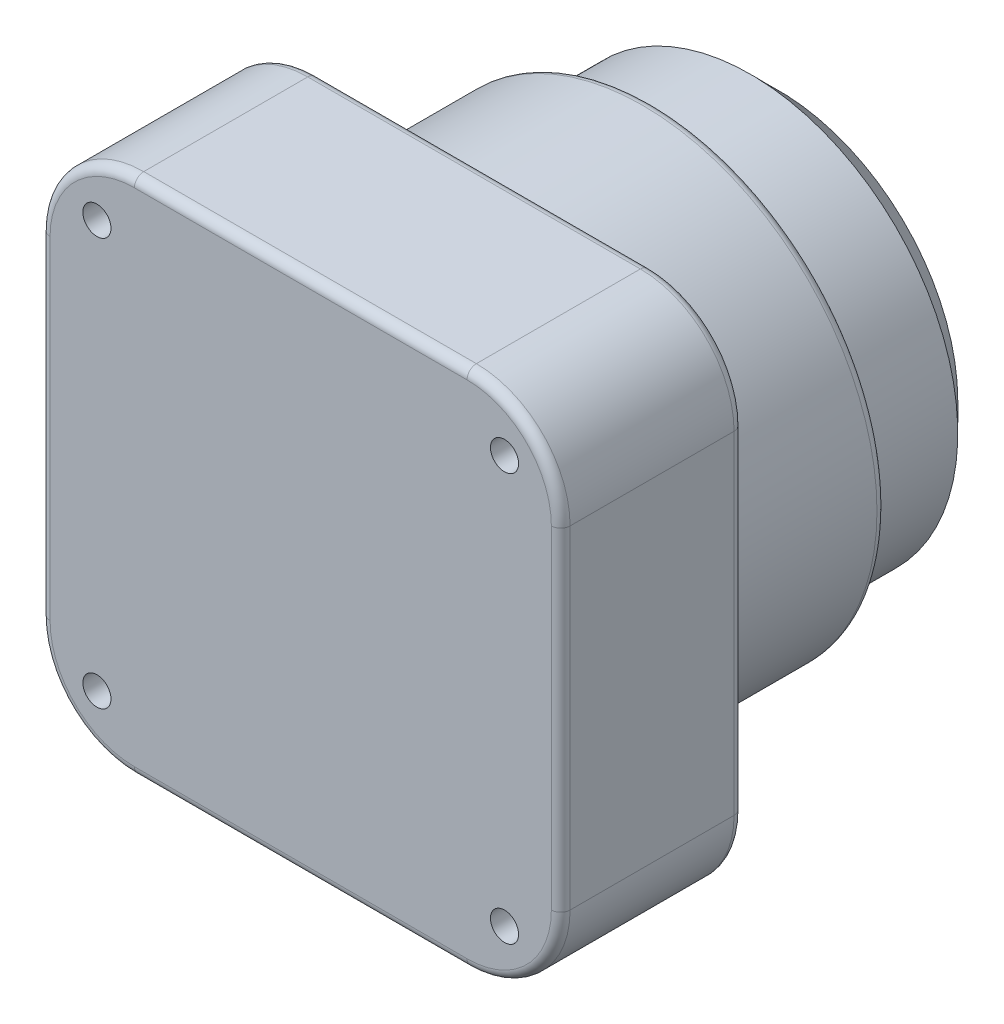
SolidWorks part; units mm, degrees
ref_plane "Plan de face" through (0, 0, 0) normal (0, 0, 1) x (1, 0, 0)
ref_plane "Plan de dessus" through (0, 0, 0) normal (0, 1, 0) x (1, 0, 0)
ref_plane "Plan de droite" through (0, 0, 0) normal (1, 0, 0) x (0, 0, -1)
sketch "Esquisse1" plane through (0, 0, 0) normal (0, 0, 1) x (1, 0, 0)
  line L1 (27.75, -27.75) -> (-27.75, -27.75)
  line L2 (27.75, -27.75) -> (27.75, 27.75)
  line L3 (27.75, 27.75) -> (-27.75, 27.75)
  line L4 (-27.75, -27.75) -> (-27.75, 27.75)
  point P0 (0, 27.75)
  point P5 (-27.75, 0)
  dimension "D1" = 55.5
extrude "Boss.-Extru.1" add sketch "Esquisse1" along normal blind 19.5
sketch "Esquisse2" plane through (0, 0, 0) normal (0, 0, -1) x (-1, 0, 0)
  circle A0 centre (0, 0) radius 25
  dimension "D1" = 50
extrude "Boss.-Extru.2" add sketch "Esquisse2" along normal blind 18
sketch "Esquisse3" plane through (0, 0, -18) normal (0, 0, -1) x (-1, 0, 0)
  circle A0 centre (0, 0) radius 22.125
  dimension "D1" = 44.25
extrude "Boss.-Extru.3" add sketch "Esquisse3" along normal blind 13.5
chamfer "Chanfrein1" distance 3 angle 45 1 edges at (-22.125, 0, -31.5)
fillet "Congé1" radius 1 11 edges at (0, 27.75, 19.5) (27.75, 0, 19.5) (0, -27.75, 19.5) (-27.75, 0, 19.5) (-27.75, 0, 0) (0, -27.75, 0) (27.75, 0, 0) (0, 27.75, 0) (-25, 0, 0) (-25, 0, -18) (-22.125, 0, -18)
fillet "Congé2" radius 10 12 edges at (-27.4571, 27.4571, 0.2929) (-27.4571, 27.4571, 19.2071) (27.4571, 27.4571, 0.2929) (27.4571, 27.4571, 19.2071) (27.4571, -27.4571, 0.2929) (27.4571, -27.4571, 19.2071) (-27.4571, -27.4571, 0.2929) (-27.4571, -27.4571, 19.2071) (-27.75, -27.75, 9.75) (27.75, -27.75, 9.75) (27.75, 27.75, 9.75) (-27.75, 27.75, 9.75)
sketch "Esquisse4" plane through (0, 0, 19.5) normal (0, 0, 1) x (1, 0, 0)
  line L1 (21.75, -21.75) -> (-21.75, -21.75) construction
  line L2 (21.75, -21.75) -> (21.75, 21.75) construction
  line L3 (21.75, 21.75) -> (-21.75, 21.75) construction
  line L4 (-21.75, -21.75) -> (-21.75, 21.75) construction
  circle A0 centre (-21.75, 21.75) radius 1.5
  circle A1 centre (21.75, 21.75) radius 1.5
  circle A2 centre (21.75, -21.75) radius 1.5
  circle A3 centre (-21.75, -21.75) radius 1.5
  point P0 (-21.75, 0)
  point P11 (0, 21.75)
  dimension "D2" = 3
  dimension "D1" = 43.5
extrude "Enlèv. mat.-Extru.1" cut sketch "Esquisse4" against normal blind 4
sketch "Esquisse5" plane through (0, -27.75, 0) normal (0, -1, 0) x (1, 0, 0)
  line L0 (17.75, 18.5) -> (-17.75, 18.5) construction
  line L1 (7.25, 16.5) -> (-7.25, 16.5)
  line L2 (7.25, 16.5) -> (7.25, 14)
  line L3 (7.25, 14) -> (-7.25, 14)
  line L4 (-7.25, 16.5) -> (-7.25, 14)
  line L5 (7.25, 16.5) -> (-7.25, 14) construction
  line L6 (7.25, 14) -> (-7.25, 16.5) construction
  point P0 (0, 15.25)
  dimension "D1" = 14.5
  dimension "D2" = 2.5
  dimension "D3" = 2
extrude "Enlèv. mat.-Extru.2" cut sketch "Esquisse5" against normal blind 4
